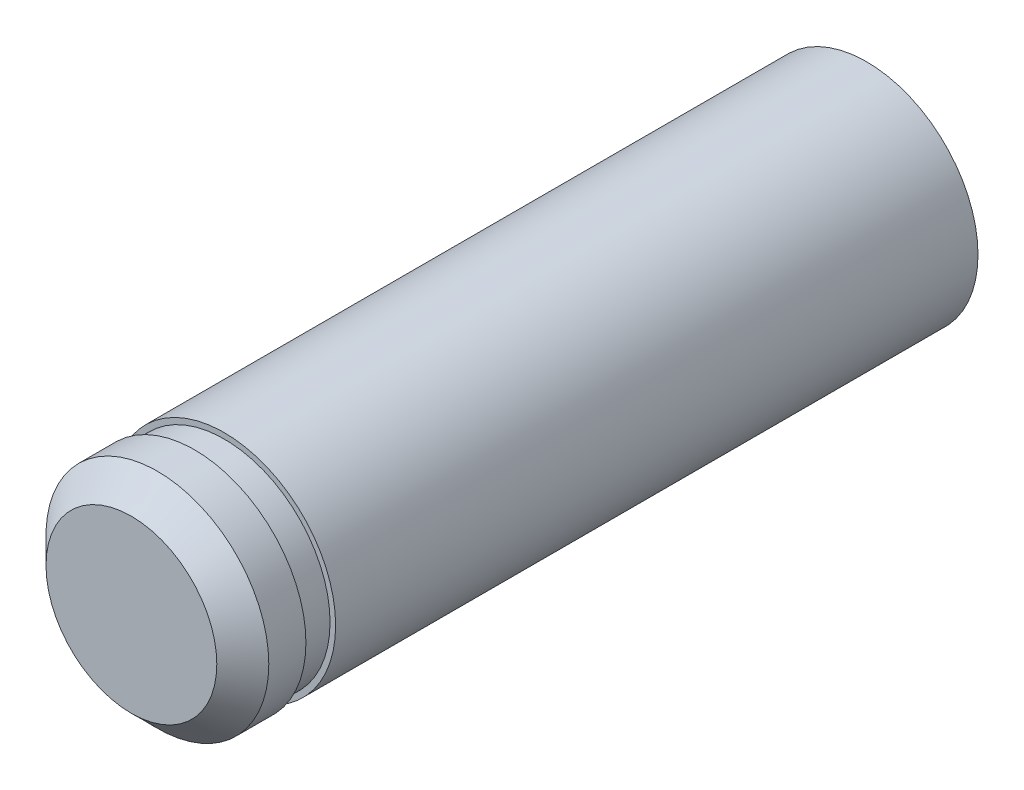
SolidWorks part; units mm, degrees
material "AISI 1020"
ref_plane "Front" through (0, 0, 0) normal (0, 0, 1) x (1, 0, 0)
ref_plane "Top" through (0, 0, 0) normal (0, 1, 0) x (1, 0, 0)
ref_plane "Right" through (0, 0, 0) normal (1, 0, 0) x (0, 0, -1)
ref_axis "side-side" through (80.9, 0, 0) along (-1, 0, 0)
ref_axis "up-down" through (0, 50, 0) along (0, -1, 0)
ref_axis "front-back" through (0, 0, -80.9) along (0, 0, 1)
sketch "Sketch2" plane through (0, 0, 0) normal (1, 0, 0) x (0, 0, -1)
  line L0 (0, 0) -> (11.0009, 0) construction
  line L1 (-18.1, 3) -> (-19.1, 3)
  line L2 (0, 0) -> (-19.8, 0)
  line L3 (0, 0) -> (0, 3)
  line L4 (0, 3) -> (-17.3, 3)
  line L5 (-19.8, 0) -> (-19.8, 2.3)
  line L6 (-19.1, 3) -> (-19.8, 2.3)
  line L7 (-18.1, 3) -> (-18.1, 2.85)
  line L8 (-18.1, 2.85) -> (-17.3, 2.85)
  line L9 (-17.3, 3) -> (-17.3, 2.85)
  line L10 (-12.8, 4.15) -> (-12, 4.15) construction
  dimension "D1" = 6
  dimension "D2" = 0.8
  dimension "D3" = 5.7
  dimension "D4" = 1
  dimension "D5" = 0.7
  dimension "D6" = 45
  dimension "D7" = 17.3
  dimension "D8" = 1.3
  dimension "D9" = 4.15
  dimension "D10" = 0.15
revolve "Revolve1" add sketch "Sketch2" angle 360 about L0
sketch "Sketch3" plane through (0, 0, 0) normal (1, 0, 0) x (0, 0, -1)
  line L0 (-19.8, 0) -> (-20.2572, 0) construction
  line L1 (-12.664, 3.3147) -> (-12.2068, 3.3147)
  line L2 (-12.664, 3.3147) -> (-12.664, 2.6035)
  line L3 (-12.664, 2.6035) -> (-12.2068, 2.6035)
  line L4 (-12.2068, 3.3147) -> (-12.2068, 2.6035)
  line L5 (-18.1, 3) -> (-19.1, 3) construction
  point P8 (-12.4354, 2.6035)
  dimension "D1" = 0.4572
  dimension "D2" = 5.207
  dimension "D3" = 0.7112
  dimension "D4" = 0.3147
